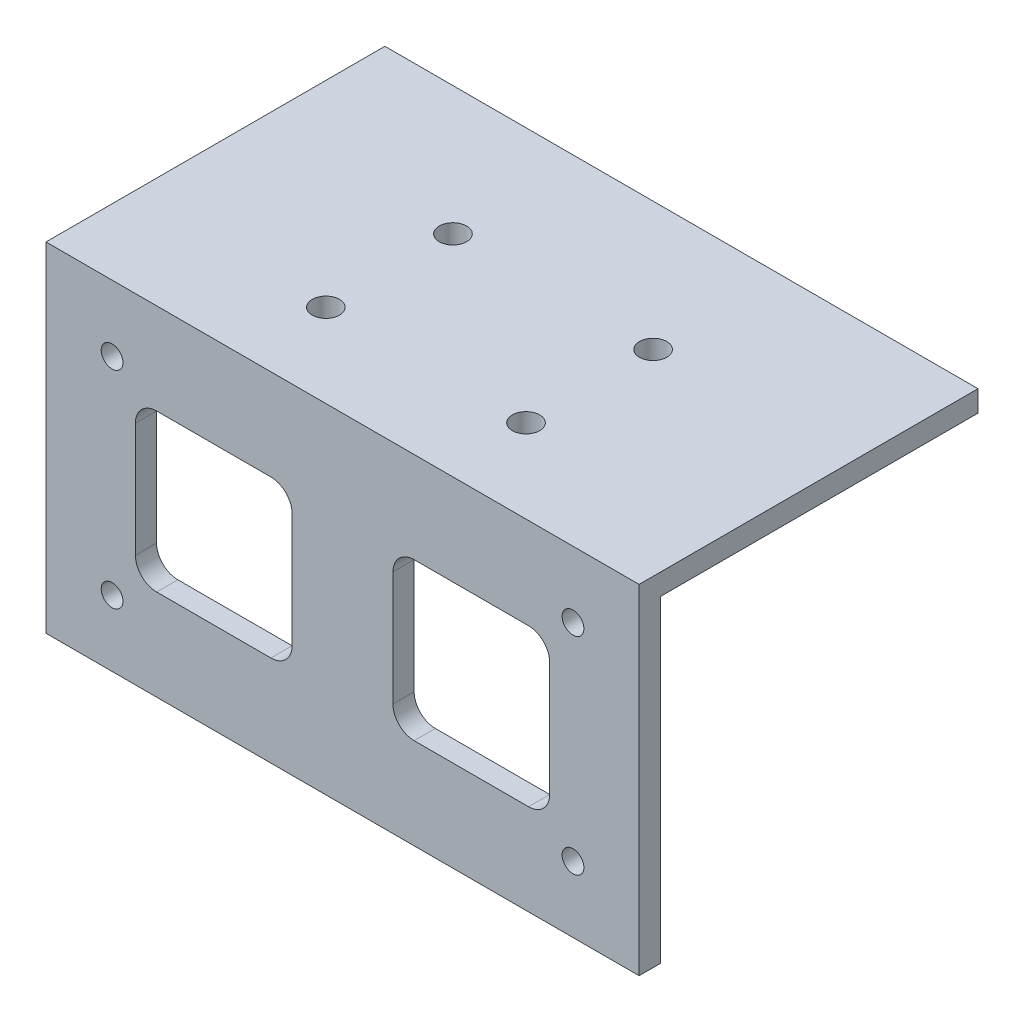
SolidWorks part; units mm, degrees
ref_plane "前视基准面" through (0, 0, 0) normal (0, 0, 1) x (1, 0, 0)
ref_plane "上视基准面" through (0, 0, 0) normal (0, 1, 0) x (1, 0, 0)
ref_plane "右视基准面" through (0, 0, 0) normal (1, 0, 0) x (0, 0, -1)
sketch "Sketch1" plane through (0, 0, 0) normal (0, 0, 1) x (1, 0, 0)
  line L0 (-76.2, 0) -> (-1.016, 0) construction
  line L1 (76.2, -38.1) -> (-76.2, -38.1) construction
  line L2 (76.2, -38.1) -> (76.2, 38.1) construction
  line L3 (76.2, 38.1) -> (-76.2, 38.1) construction
  line L4 (-76.2, -38.1) -> (-76.2, 38.1) construction
  line L5 (76.2, -38.1) -> (-76.2, 38.1) construction
  line L6 (76.2, 38.1) -> (-76.2, -38.1) construction
  line L7 (-88.9, 50.8) -> (-88.9, -50.8)
  line L8 (-76.2, 38.1) -> (76.2, 38.1)
  line L9 (88.9, 50.8) -> (88.9, -50.8)
  line L10 (-88.9, 50.8) -> (88.9, 50.8)
  line L11 (0, 50.8) -> (0, 38.1) construction
  line L12 (-76.2, -38.1) -> (76.2, -38.1)
  line L14 (-88.9, -50.8) -> (88.9, -50.8)
  line L15 (-62.103, 23.495) -> (-15.113, 23.495)
  line L16 (-62.103, 23.495) -> (-62.103, -23.495)
  line L17 (-62.103, -23.495) -> (-15.113, -23.495)
  line L18 (-15.113, 23.495) -> (-15.113, -23.495)
  line L19 (15.113, 23.495) -> (62.103, 23.495)
  line L20 (15.113, 23.495) -> (15.113, -23.495)
  line L21 (15.113, -23.495) -> (62.103, -23.495)
  line L22 (62.103, 23.495) -> (62.103, -23.495)
  circle A0 centre (-69.088, 30.988) radius 3.2639
  circle A1 centre (69.088, 30.988) radius 3.2639
  circle A2 centre (69.088, -30.988) radius 3.2639
  circle A3 centre (-69.088, -30.988) radius 3.2639
  circle A4 centre (-38.608, 0) radius 23.495 construction
  circle A5 centre (38.608, 0) radius 23.495 construction
  point P0 (0, 0)
  dimension "D8" = 6.5278
  dimension "D11" = 46.99
  dimension "D12" = 46.99
  dimension "D1" = 76.2
  dimension "D2" = 152.4
  dimension "D3" = 30.988
  dimension "D4" = 30.988
  dimension "D5" = 69.088
  dimension "D6" = 69.088
  dimension "D9" = 38.608
  dimension "D10" = 38.608
  dimension "D13" = 12.7
  dimension "D14" = 101.6
  dimension "D15" = 12.7
extrude "Boss-Extrude2" add sketch "Sketch1" along normal blind 6.35 contours L3 L10 | L4 L1 L2 L3 A5 A4 A2 A1 A0 A3 | L1 L14 region at (0, 0, 0)
sketch "Sketch2" plane through (0, 0, 0) normal (0, 0, -1) x (-1, 0, 0)
  line L1 (-88.9, 50.8) -> (88.9, 50.8)
  line L2 (-88.9, 50.8) -> (-88.9, 44.45)
  line L3 (-88.9, 44.45) -> (88.9, 44.45)
  line L4 (88.9, 50.8) -> (88.9, 44.45)
  line L5 (-88.9, 50.8) -> (-88.9, -50.8) construction
  line L6 (88.9, 50.8) -> (88.9, -50.8) construction
  line L7 (88.9, 50.8) -> (-88.9, 50.8) construction
  dimension "D1" = 6.35
extrude "Boss-Extrude3" add sketch "Sketch2" along normal blind 95.25
sketch "Sketch3" plane through (0, 50.8, 0) normal (0, 1, 0) x (1, 0, 0)
  line L0 (0, 95.25) -> (0, -6.35) construction
  line L1 (-88.9, 95.25) -> (88.9, 95.25) construction
  line L2 (-88.9, -6.35) -> (88.9, -6.35) construction
  circle A0 centre (-30, 18.65) radius 4.1021
  circle A1 centre (-30, 56.75) radius 4.1021
  circle A2 centre (30, 18.65) radius 4.1021
  circle A3 centre (30, 56.75) radius 4.1021
  dimension "D5" = 8.2042
  dimension "D1" = 25
  dimension "D2" = 38.1
  dimension "D3" = 30
  dimension "D4" = 30
fillet "Fillet1" radius 6.35 8 edges at (-62.103, -23.495, 3.175) (15.113, -23.495, 3.175) (15.113, 23.495, 3.175) (62.103, 23.495, 3.175) (62.103, -23.495, 3.175) (-15.113, -23.495, 3.175) (-15.113, 23.495, 3.175) (-62.103, 23.495, 3.175)
extrude "Cut-Extrude1" cut sketch "Sketch3" against normal through all
